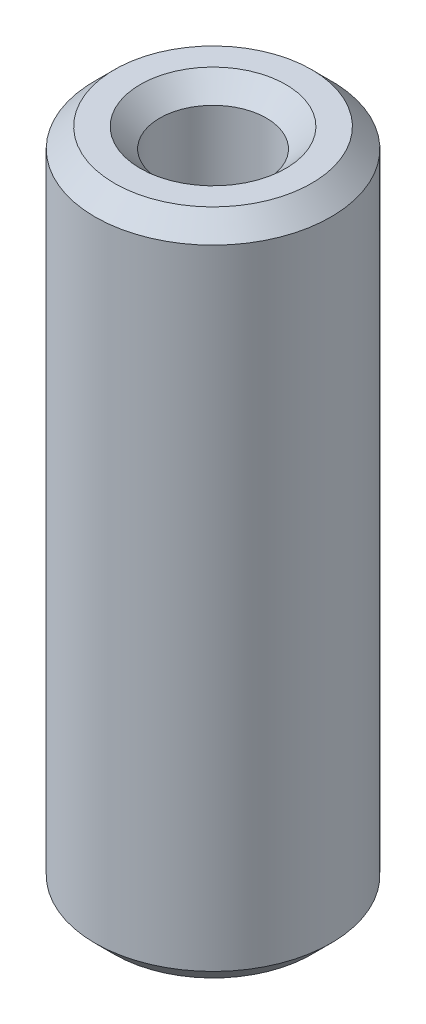
SolidWorks part; units mm, degrees
ref_plane "Front Plane" through (0, 0, 0) normal (0, 0, 1) x (1, 0, 0)
ref_plane "Top Plane" through (0, 0, 0) normal (0, 1, 0) x (1, 0, 0)
ref_plane "Right Plane" through (0, 0, 0) normal (1, 0, 0) x (0, 0, -1)
sketch "Sketch1" plane through (0, 0, 0) normal (0, 1, 0) x (1, 0, 0)
  circle A0 centre (0, 0) radius 22.5
  dimension "SLEEVE_OD" = 45
extrude "Boss-Extrude1" add sketch "Sketch1" along normal blind 127.3626
sketch "Sketch2" plane through (0, 0, 0) normal (0, 1, 0) x (1, 0, 0)
  circle A0 centre (0, 0) radius 10.1755
  dimension "BORE_D" = 20.351
extrude "Cut-Extrude1" cut sketch "Sketch2" along normal through all
chamfer "Chamfer1" distance 3.7013 angle 45 4 edges at (0, 127.3626, 10.1755) (0, 0, 10.1755) (0, 0, 22.5) (0, 127.3626, 22.5)
